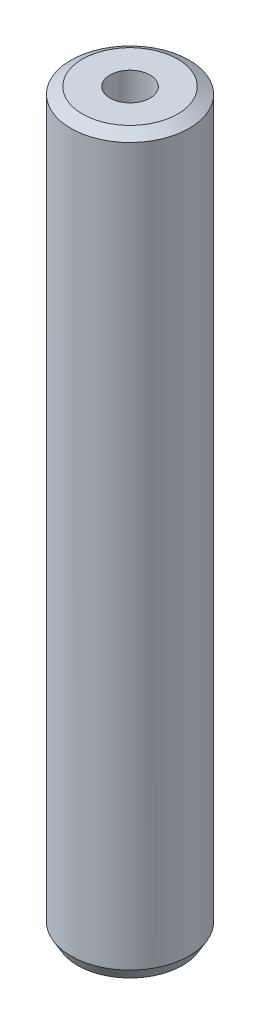
SolidWorks part; units mm, degrees
ref_plane "Front Plane" through (0, 0, 0) normal (0, 0, 1) x (1, 0, 0)
ref_plane "Top Plane" through (0, 0, 0) normal (0, 1, 0) x (1, 0, 0)
ref_plane "Right Plane" through (0, 0, 0) normal (1, 0, 0) x (0, 0, -1)
sketch "Sketch1" plane through (0, 0, 0) normal (0, 1, 0) x (1, 0, 0)
  circle A0 centre (0, 0) radius 37.5
  dimension "SHAFT_OD" = 75
extrude "Boss-Extrude1" add sketch "Sketch1" along normal blind 465.9428
sketch "Sketch2" plane through (0, 0, 0) normal (0, 1, 0) x (1, 0, 0)
  circle A0 centre (0, 0) radius 12.6957
  dimension "BORE_D" = 25.3914
extrude "Cut-Extrude1" cut sketch "Sketch2" along normal through all
chamfer "Chamfer1" distance 4.226 angle 60 2 edges at (0, 465.9428, 37.5) (0, 0, 37.5) first distance on face at (0, 465.9428, 37.5) first distance on face at (0, 0, 12.6957)
